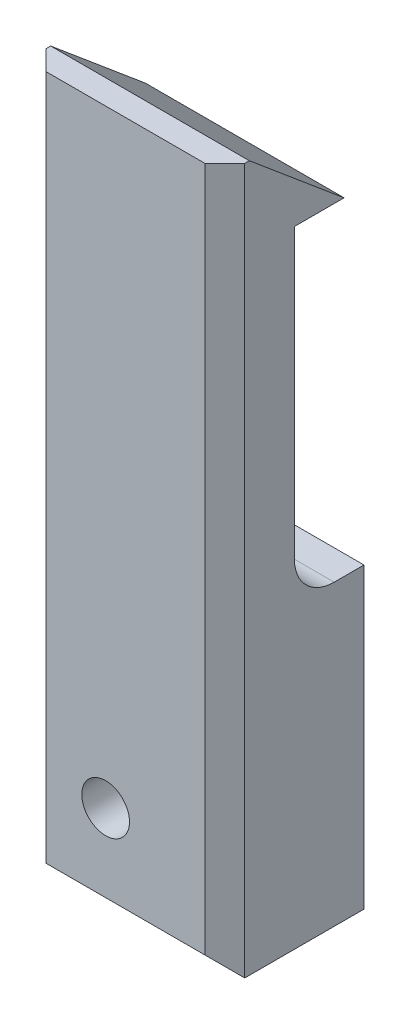
SolidWorks part; units mm, degrees
ref_plane "前视基准面" through (0, 0, 0) normal (0, 0, 1) x (1, 0, 0)
ref_plane "上视基准面" through (0, 0, 0) normal (0, 1, 0) x (1, 0, 0)
ref_plane "右视基准面" through (0, 0, 0) normal (1, 0, 0) x (0, 0, -1)
ref_plane "基准面4" through (3, 0, 0) normal (1, 0, 0) x (0, 0, -1)
sketch "草图3" plane through (3, 0, 0) normal (1, 0, 0) x (0, 0, -1)
  line L0 (0, -25.4015) -> (-7, -25.4015)
  line L1 (-7, -25.4015) -> (-7, 11.1331)
  line L2 (-7, 11.1331) -> (-1, 6.0985)
  line L3 (-1, 6.0985) -> (-3.5, 6.0985)
  line L4 (-3.5, 6.0985) -> (-3.5, -8.4015)
  line L5 (-1.5, -10.4015) -> (0, -10.4015)
  line L6 (0, -10.4015) -> (0, -25.4015)
  line L7 (144.1721, 5.5985) -> (-3, 5.5985) construction
  line L8 (-3, 2.0985) -> (-3, 5.5985) construction
  line L9 (-5.767, 10.0985) -> (-7, 10.0985)
  arc A0 (-3.5, -8.4015) -> (-1.5, -10.4015) centre (-1.5, -8.4015) ccw
  dimension "D7" = 2
  dimension "D1" = 0.5
  dimension "D2" = 0.5
  dimension "D3" = 2
  dimension "D4" = 3.5
  dimension "D5" = 40
  dimension "D6" = 4
extrude "凸台-拉伸1" add sketch "草图3" against normal blind 10 contours A0 L4 L3 L2 L9 L1 L0 L6 L5 region at (3, -10.679, 4.1815)
sketch "草图5" plane through (0, 0, 7) normal (0, 0, 1) x (1, 0, 0)
  point P0 (-3, -20.5)
  point P2 (-1, -26.5)
hole_wizard "M2 间隙孔1" positions "草图6" profile "草图7" hole size "M2" standard "GB" end condition through all
sketch "草图6" plane through (0, 0, 7) normal (0, 0, 1) x (1, 0, 0)
  point P0 (-1, -26.5)
  point P3 (-3, -20.5)
sketch "草图7" plane through (-1, -26.5, 7) normal (1, 0, 0) x (0, -1, 0)
  line L0 (0, 0) -> (0, 7)
  line L1 (0, 7) -> (1.2, 7)
  line L2 (1.2, 7) -> (1.2, 0)
  line L5 (1.2, 0) -> (0, 0)
  line L11 (0, -6.35) -> (0, 107.95) construction
  dimension "通孔孔直径" = 2.4
  dimension "通孔孔深度" = 7
chamfer "倒角1" distance 1 angle 45 4 edges at (-7, -7.6515, 7) (3, -7.6515, 7) (-4.2415, -25.4015, 7) (1.2415, -25.4015, 7)
